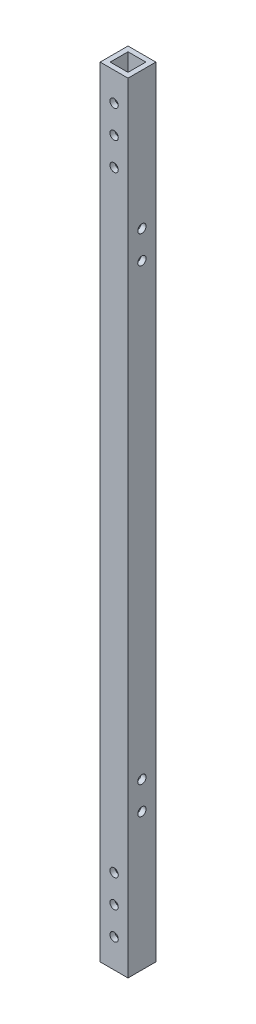
SolidWorks part; units mm, degrees
ref_plane "前视基准面" through (0, 0, 0) normal (0, 0, 1) x (1, 0, 0)
ref_plane "上视基准面" through (0, 0, 0) normal (0, 1, 0) x (1, 0, 0)
ref_plane "右视基准面" through (0, 0, 0) normal (1, 0, 0) x (0, 0, -1)
sketch "草图1" plane through (0, 0, 0) normal (0, 1, 0) x (1, 0, 0)
  line L1 (-5, 5) -> (5, 5)
  line L2 (-5, 5) -> (-5, -5)
  line L3 (-5, -5) -> (5, -5)
  line L4 (5, 5) -> (5, -5)
  line L5 (-5, 5) -> (5, -5) construction
  line L6 (-5, -5) -> (5, 5) construction
  line L7 (-3.2, 3.2) -> (3.2, 3.2)
  line L8 (-3.2, 3.2) -> (-3.2, -3.2)
  line L9 (-3.2, -3.2) -> (3.2, -3.2)
  line L10 (3.2, 3.2) -> (3.2, -3.2)
  line L11 (-3.2, 3.2) -> (3.2, -3.2) construction
  line L12 (-3.2, -3.2) -> (3.2, 3.2) construction
  point P0 (0, 0)
  point P6 (0, 0)
  dimension "D1" = 1.8
  dimension "D2" = 10
extrude "凸台-拉伸1" add sketch "草图1" along normal mid plane 280
sketch "草图2" plane through (0, 0, -5) normal (0, 0, -1) x (-1, 0, 0)
  line L0 (0, 0) -> (-31.6693, 0) construction
  line L1 (0, 6.5147) -> (0, -25.163) construction
  line L2 (-14.614, -99.7) -> (84.614, -99.7) construction
  circle A3 centre (0, -129.7) radius 1.5
  circle A4 centre (0, -119.7) radius 1.5
  circle A5 centre (0, -109.7) radius 1.5
  circle A6 centre (0, 119.7) radius 1.5
  circle A7 centre (0, 129.7) radius 1.5
  circle A8 centre (0, 109.7) radius 1.5
  dimension "D4" = 3
  dimension "D1" = 10
  dimension "D2" = 10
  dimension "D3" = 10
extrude "切除-拉伸1" cut sketch "草图2" against normal through all
sketch "草图3" plane through (-5, 0, 0) normal (-1, 0, 0) x (0, 0, 1)
  line L0 (0, 0) -> (-37.9958, 0) construction
  circle A0 centre (0, -90.7) radius 1.5
  circle A1 centre (0, -80.7) radius 1.5
  circle A2 centre (0, 80.7) radius 1.5
  circle A3 centre (0, 90.7) radius 1.5
  dimension "D1" = 3
extrude "切除-拉伸2" cut sketch "草图3" against normal through all
